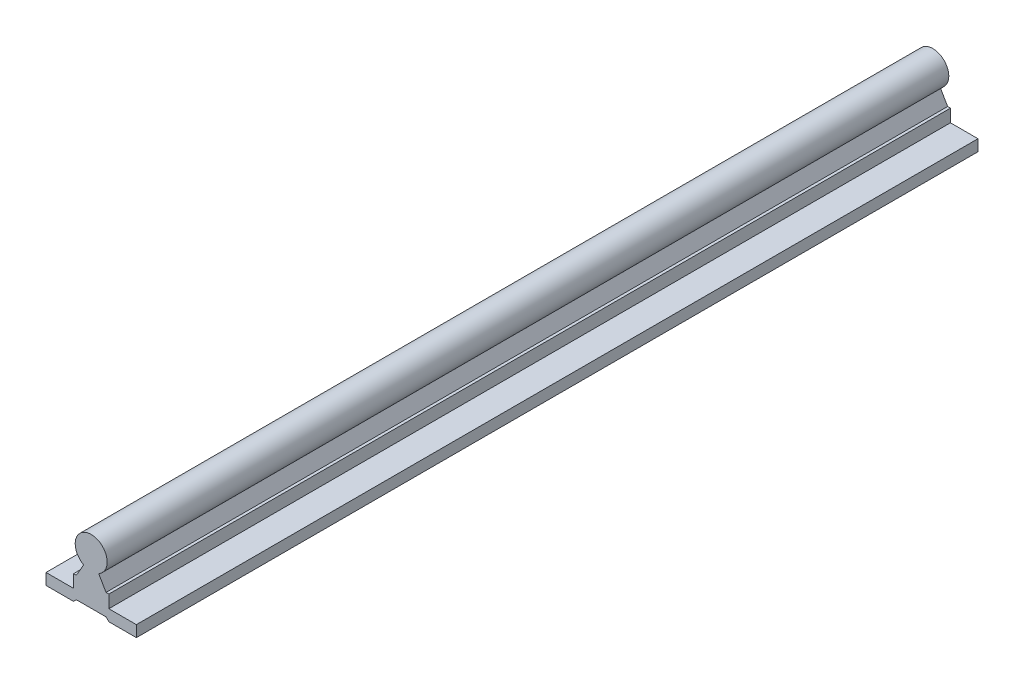
SolidWorks part; units mm, degrees
ref_plane "前视基准面" through (0, 0, 0) normal (0, 0, 1) x (1, 0, 0)
ref_plane "上视基准面" through (0, 0, 0) normal (0, 1, 0) x (1, 0, 0)
ref_plane "右视基准面" through (0, 0, 0) normal (1, 0, 0) x (0, 0, -1)
sketch "草图1" plane through (0, 0, 0) normal (0, 0, 1) x (1, 0, 0)
  line L0 (0, -207.286) -> (0, 10157.0132) construction
  line L1 (-16, 0) -> (16, 0)
  line L2 (-16, 0) -> (-16, 4)
  line L3 (-16, 4) -> (-6.25, 4)
  line L4 (-6.25, 4) -> (-6.25, 8.5)
  line L5 (6.25, 4) -> (16, 4)
  line L6 (16, 0) -> (16, 4)
  line L7 (6.25, 4) -> (6.25, 8.5)
  line L8 (-6.25, 8.5) -> (-5.25, 8.5)
  line L9 (6.25, 8.5) -> (5.25, 8.5)
  line L10 (-1000, 13) -> (49000, 13) construction
  line L11 (-2.6519, 13) -> (-5.25, 8.5)
  line L12 (5.25, 8.5) -> (2.6519, 13)
  arc A0 (-2.6519, 13) -> (2.6519, 13) centre (0, 18) cw
  dimension "D1" = 16
  dimension "D2" = 32
  dimension "D3" = 6.25
  dimension "D4" = 12.5
  dimension "D5" = 8.5
  dimension "D6" = 8.5
  dimension "D7" = 1
  dimension "D8" = 1
  dimension "D9" = 13
  dimension "D10" = 30
  dimension "D11" = 4
  dimension "D12" = 60
  dimension "D13" = 18
extrude "凸台-拉伸1" add sketch "草图1" along normal mid plane 298
sketch "草图2" plane through (0, 0, 149) normal (0, 0, 1) x (1, 0, 0)
  line L0 (-5.25, 0) -> (-5.25, 1)
  line L1 (-16, 0) -> (16, 0) construction
  line L2 (-5.25, 1) -> (5.25, 1)
  line L3 (5.25, 1) -> (5.25, 0)
  line L4 (-5.25, 0) -> (5.25, 0)
  dimension "D1" = 1
extrude "切除-拉伸1" cut sketch "草图2" against normal through all
chamfer "倒角1" distance 1 angle 45 2 edges at (5.25, 0, 0) (-5.25, 0, 0)
